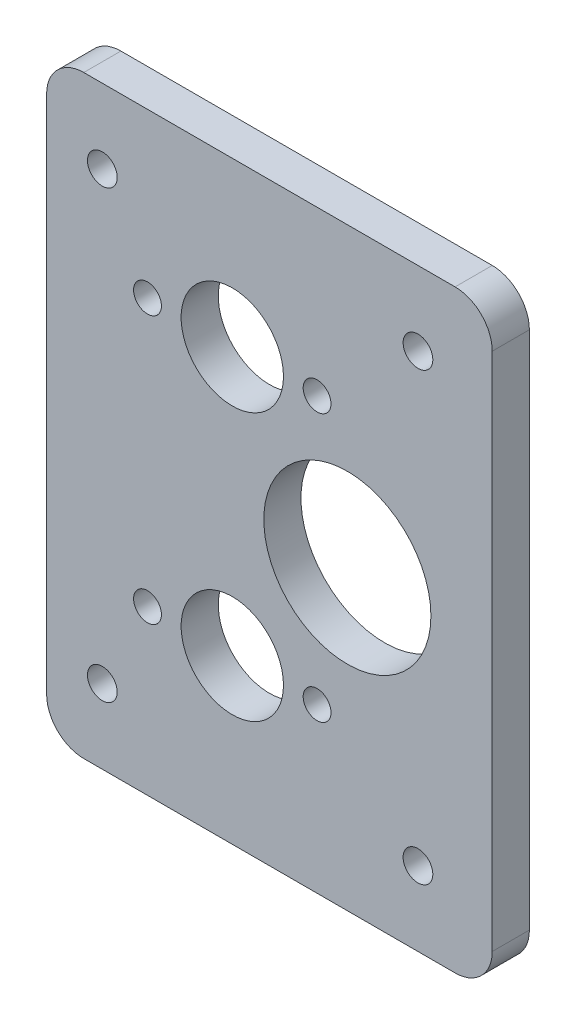
SolidWorks part; units mm, degrees
ref_plane "Front Plane" through (0, 0, 0) normal (0, 0, 1) x (1, 0, 0)
ref_plane "Top Plane" through (0, 0, 0) normal (0, 1, 0) x (1, 0, 0)
ref_plane "Right Plane" through (0, 0, 0) normal (1, 0, 0) x (0, 0, -1)
sketch "Sketch1" plane through (0, 0, 0) normal (0, 0, 1) x (1, 0, 0)
  line L0 (0, 0) -> (0, -45.72)
  line L1 (0, 0) -> (19.6773, -22.86)
  line L2 (-25.4, 27.94) -> (38.1, 27.94)
  line L3 (-31.75, 21.59) -> (-31.75, -67.31)
  line L4 (-25.4, -73.66) -> (38.1, -73.66)
  line L5 (44.45, 21.59) -> (44.45, -67.31)
  line L6 (0, -45.72) -> (19.6773, -22.86)
  circle A0 centre (0, 0) radius 14.5
  circle A1 centre (0, 0) radius 22.225
  circle A2 centre (0, -45.72) radius 22.15
  circle A3 centre (0, -45.72) radius 14.5
  circle A4 centre (14.5, 0) radius 2.3812
  circle A5 centre (-14.5, 0) radius 2.3813
  circle A6 centre (14.5, -45.72) radius 2.3812
  circle A7 centre (-14.5, -45.72) radius 2.3813
  circle A8 centre (19.6773, -22.86) radius 14.2875
  arc A9 (-31.75, -67.31) -> (-25.4, -73.66) centre (-25.4, -67.31) ccw
  circle A10 centre (0, -45.72) radius 8.75
  circle A11 centre (0, 0) radius 8.75
  arc A12 (38.1, -73.66) -> (44.45, -67.31) centre (38.1, -67.31) ccw
  arc A13 (38.1, 27.94) -> (44.45, 21.59) centre (38.1, 21.59) cw
  arc A14 (-25.4, 27.94) -> (-31.75, 21.59) centre (-25.4, 21.59) ccw
  point P0 (0, 0)
  point P16 (0, -22.86)
  dimension "D1" = 29
  dimension "D2" = 44.45
  dimension "D4" = 44.3
  dimension "D5" = 29
  dimension "D6" = 4.7625
  dimension "D7" = 4.7625
  dimension "D8" = 4.7625
  dimension "D9" = 4.7625
  dimension "D16" = 30.1625
  dimension "D17" = 17.5
  dimension "D18" = 17.5
  dimension "D20" = 28.575
  dimension "D21" = 6.35
  dimension "D3" = 45.72
  dimension "D10" = 31.75
  dimension "D11" = 50.8
  dimension "D12" = 50.8
  dimension "D13" = 44.45
  dimension "D14" = 30.1625
  dimension "D15" = 0
  dimension "D19" = 0
extrude "Boss-Extrude1" add sketch "Sketch1" along normal blind 6.35 contours L5 L2 L3 L4 A8 A2 L0 A1 | A8 A1 L0 A0 A5 A4 L1 | L1 A0 A4 A5 L0 | L0 A0 L1 | A8 L1 A0 L0 A1 | A8 A2 L0 A3 L6 | A8 A1 L0 A2 | A8 L6 A3 A6 A7 L0 A2 | A10 L0 A3 A7 A6 L6 | A10 L6 A3 L0 region at (4.0408, -10.8883, 0) region at (-0.4074, -11.625, 0) region at (3.8849, -17.17, 0) region at (-0.6286, -18.3625, 0) region at (3.0423, -22.8984, 0) region at (3.8931, -28.5845, 0) region at (-0.6265, -27.395, 0) region at (4.0408, -34.8317, 0) region at (-0.4074, -34.095, 0) region at (6.35, 26.67, 0)
sketch "Sketch2" plane through (0, 0, 6.35) normal (0, 0, 1) x (1, 0, 0)
  line L4 (38.1, 27.94) -> (-25.4, 27.94)
  line L5 (-31.75, 21.59) -> (-31.75, -67.31)
  line L6 (-25.4, -73.66) -> (38.1, -73.66)
  line L7 (44.45, -67.31) -> (44.45, 21.59)
  line L8 (38.1, 27.94) -> (-25.4, 27.94)
  line L9 (-31.75, 21.59) -> (-31.75, -67.31)
  line L10 (-25.4, -73.66) -> (38.1, -73.66)
  line L11 (44.45, -67.31) -> (44.45, 21.59)
  arc A4 (-25.4, 27.94) -> (-31.75, 21.59) centre (-25.4, 21.59) ccw
  arc A5 (-31.75, -67.31) -> (-25.4, -73.66) centre (-25.4, -67.31) ccw
  arc A6 (38.1, -73.66) -> (44.45, -67.31) centre (38.1, -67.31) ccw
  arc A7 (44.45, 21.59) -> (38.1, 27.94) centre (38.1, 21.59) ccw
  arc A8 (-25.4, 27.94) -> (-31.75, 21.59) centre (-25.4, 21.59) ccw
  arc A9 (-31.75, -67.31) -> (-25.4, -73.66) centre (-25.4, -67.31) ccw
  arc A10 (38.1, -73.66) -> (44.45, -67.31) centre (38.1, -67.31) ccw
  arc A11 (44.45, 21.59) -> (38.1, 27.94) centre (38.1, 21.59) ccw
  circle A16 centre (-22.225, 15.24) radius 2.54
  circle A17 centre (31.75, 15.24) radius 2.54
  circle A18 centre (31.75, -60.96) radius 2.54
  circle A19 centre (-22.225, -60.96) radius 2.54
  dimension "D2" = 5.08
  dimension "D5" = 5.08
  dimension "D6" = 5.08
  dimension "D9" = 12.7
  dimension "D11" = 5.08
  dimension "D3" = 12.7
  dimension "D4" = 9.525
  dimension "D7" = 12.7
  dimension "D8" = 12.7
  dimension "D10" = 12.7
  dimension "D12" = 12.7
  dimension "D13" = 9.525
  dimension "D1" = 0
extrude "Cut-Extrude1" cut sketch "Sketch2" against normal up to surface (6.35 mm away) contours A16 | A17 | A18 | A19 up to face at (8.75, -45.72, 0)
